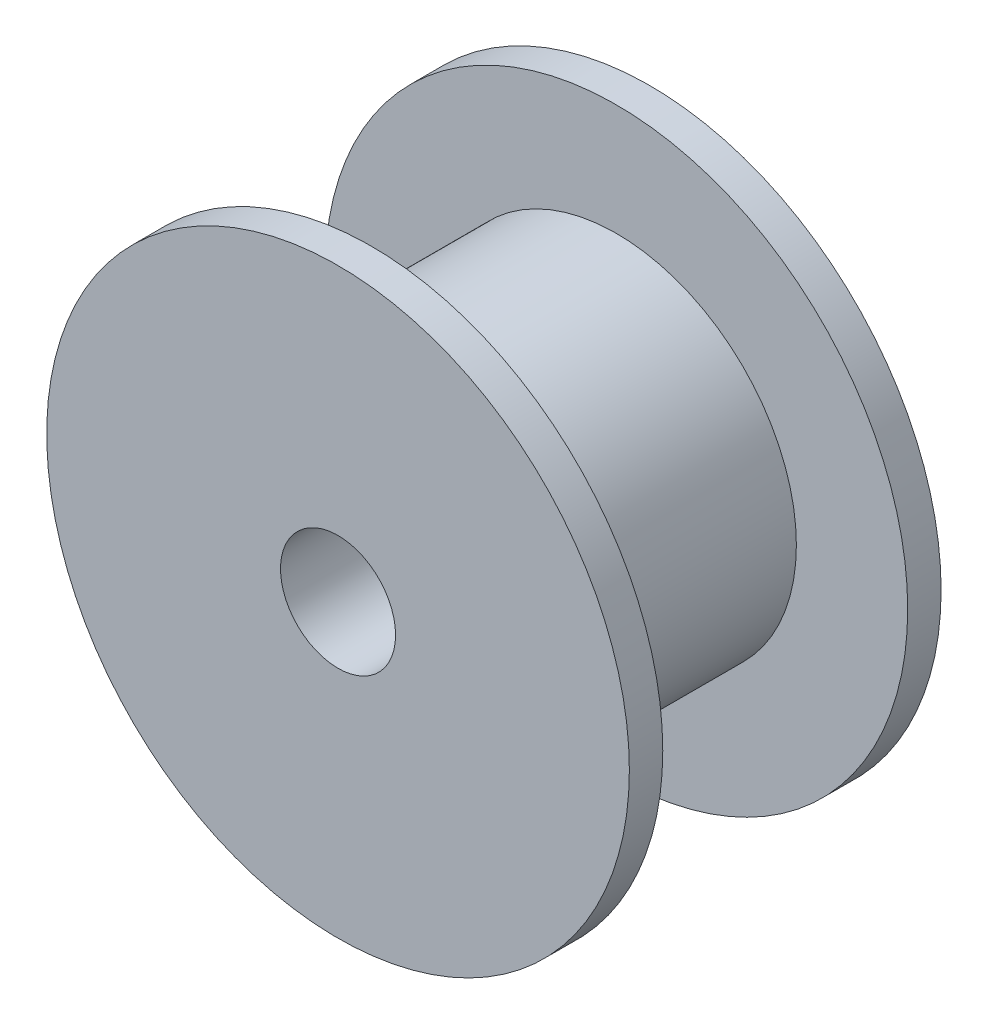
SolidWorks part; units mm, degrees
ref_plane "Front Plane" through (0, 0, 0) normal (0, 0, 1) x (1, 0, 0)
ref_plane "Top Plane" through (0, 0, 0) normal (0, 1, 0) x (1, 0, 0)
ref_plane "Right Plane" through (0, 0, 0) normal (1, 0, 0) x (0, 0, -1)
sketch "Sketch1" plane through (0, 0, 0) normal (0, 0, 1) x (1, 0, 0)
  circle A0 centre (0, 0) radius 1.55
  circle A1 centre (0, 0) radius 4.85
  circle A2 centre (0, 0) radius 7.85
  dimension "D1" = 9.7
  dimension "D2" = 3.1
  dimension "D3" = 3
extrude "Boss-Extrude1" add sketch "Sketch1" along normal mid plane 8.4 contours A1 A0 region at (-4.7128, 0, 0)
extrude "Boss-Extrude2" add sketch "Sketch1<3>" against normal blind 0.9 from surface contours A2 A1 region at (-7.628, 0, 0) starting at face at (1.55, 0, 4.2)
sketch "Sketch1<3>" plane through (0, 0, 0) normal (0, 0, 1) x (1, 0, 0) same geometry as "Sketch1"
extrude "Boss-Extrude3" add sketch "Sketch1<4>" along normal blind 0.9 from surface contours A2 A1 region at (-7.628, 0, 0) starting at face at (1.55, 0, -4.2)
sketch "Sketch1<4>" plane through (0, 0, 0) normal (0, 0, 1) x (1, 0, 0) same geometry as "Sketch1"
